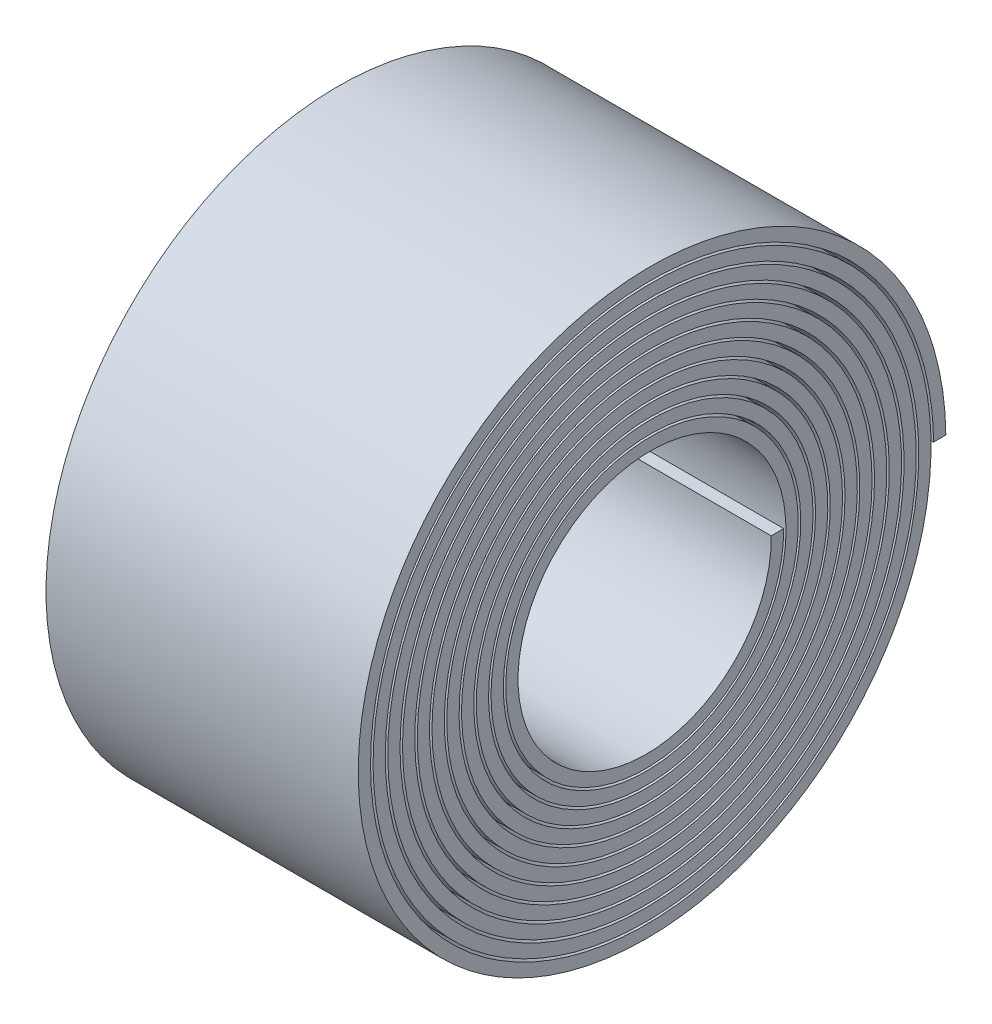
SolidWorks part; units mm, degrees
ref_plane "Front Plane" through (0, 0, 0) normal (0, 0, 1) x (1, 0, 0)
ref_plane "Top Plane" through (0, 0, 0) normal (0, 1, 0) x (1, 0, 0)
ref_plane "Right Plane" through (0, 0, 0) normal (1, 0, 0) x (0, 0, -1)
sketch "Sketch1" plane through (0, 0, 0) normal (1, 0, 0) x (0, 0, -1)
  circle A0 centre (0, 0) radius 2.5
  point P2 (0, 0)
  dimension "D1" = 5
curve "Helix/Spiral1"
sketch "Sketch2" plane through (0, 0, 0) normal (1, 0, 0) x (0, 0, -1)
  line L0 (2.5, 0) -> (2.75, 0.0048)
  line L2 (5.8, 0) -> (6.05, 0.0021)
  spline S0 degree 3 poles (-421.9366, -905.3575) (-57.6424, 57.3436) (7.9155, 8.7178) (1.9401, -1.6929) (1.6038, -2.0262) (0.8018, -2.4743) (0.3373, -2.5884) (-0.5902, -2.5601) (-1.0519, -2.4176) (-1.8406, -1.9113) (-2.1664, -1.5481) (-2.5866, -0.6999) (-2.6802, -0.2161) (-2.6036, 0.7366) (-2.4335, 1.2041) (-1.8725, 1.9894) (-1.4824, 2.3059) (-0.5889, 2.6946) (-0.0868, 2.7661) (0.8885, 2.6388) (1.3604, 2.4401) (2.1387, 1.8236) (2.444, 1.4066) (2.7978, 0.4689) (2.8456, -0.0505) (2.6652, -1.0457) (2.437, -1.5201) (1.7644, -2.2878) (1.3208, -2.58) (0.3402, -2.8954) (-0.1953, -2.9181) (-1.2075, -2.6823) (-1.6827, -2.424) (-2.4362, -1.6949) (-2.7134, -1.2249) (-2.9871, -0.203) (-2.9831, 0.3474) (-2.6898, 1.3734) (-2.4008, 1.8476) (-1.6149, 2.5831) (-1.119, 2.8434) (-0.0577, 3.072) (0.5063, 3.0399) (1.5429, 2.6873) (2.0141, 2.3671) (2.7278, 1.5245) (2.9693, 1.0032) (3.1497, -0.0956) (3.0882, -0.6716) (2.6745, -1.7154) (2.3227, -2.1817) (1.4237, -2.8698) (0.8778, -3.0906) (-0.2563, -3.2195) (-0.8428, -3.1274) (-1.8902, -2.651) (-2.3496, -2.2674) (-3.0082, -1.3126) (-3.2065, -0.7428) (-3.281, 0.4241) (-3.1571, 1.0194) (-2.6168, 2.0667) (-2.2011, 2.5172) (-1.1912, 3.1425) (-0.5985, 3.3164) (0.5985, 3.3336) (1.2009, 3.1767) (2.2444, 2.5714) (2.6838, 2.1236) (3.2719, 1.0598) (3.4197, 0.4451) (3.3768, -0.779) (3.186, -1.3868) (2.5147, -2.4224) (2.035, -2.8487) (0.9184, -3.3959) (0.2831, -3.5158) (-0.9652, -3.4101) (-1.5763, -3.1846) (-2.6001, -2.4467) (-3.0113, -1.9353) (-3.5136, -0.7674) (-3.604, -0.1126) (-3.4331, 1.1565) (-3.172, 1.769) (-2.3671, 2.7768) (-1.8243, 3.1707) (-0.6071, 3.6246) (0.0658, 3.6837) (1.3523, 3.4454) (1.9641, 3.148) (2.9519, 2.276) (3.3264, 1.7023) (3.728, 0.4376) (3.7545, -0.2517) (3.4465, -1.552) (3.1124, -2.1611) (2.1732, -3.1246) (1.5694, -3.4776) (0.2594, -3.8234) (-0.4448, -3.8157) (-1.755, -3.4362) (-2.3591, -3.0649) (-3.2941, -2.0589) (-3.6235, -1.4256) (-3.9101, -0.073) (-3.8667, 0.6444) (-3.414, 1.9607) (-3.0053, 2.5576) (-1.9331, 3.4598) (-1.2712, 3.7636) (0.1214, 3.9875) (0.8501, 3.9072) (2.1683, 3.3799) (2.7558, 2.9334) (3.6209, 1.7959) (3.897, 1.1064) (4.0551, -0.3232) (3.9367, -1.0613) (3.3334, -2.3772) (2.8492, -2.953) (1.6475, -3.7767) (0.9316, -4.0232) (-0.5319, -4.1123) (-1.2774, -3.9547) (-2.5866, -3.2743) (-3.1485, -2.7526) (-3.9265, -1.488) (-4.1414, -0.7469) (-4.1586, 0.7469) (-3.9607, 1.4977) (-3.2027, 2.7959) (-2.6435, 3.3414) (-1.3177, 4.0695) (-0.5529, 4.251) (0.9678, 4.1935) (1.7216, 3.9545) (3.0042, 3.1182) (3.531, 2.522) (4.2051, 1.1369) (4.3513, 0.35) (4.2166, -1.1938) (3.9357, -1.9485) (3.0209, -3.2108) (2.3882, -3.7167) (0.946, -4.3326) (0.1385, -4.4418) (-1.4244, -4.2274) (-2.1776, -3.9039) (-3.415, -2.9106) (-3.8975, -2.2421) (-4.4513, -0.7452) (-4.5218, 0.0811) (-4.2255, 1.6589) (-3.859, 2.4081) (-2.7875, 3.616) (-2.0839, 4.0728) (-0.535, 4.5606) (0.3082, 4.5908) (1.4994, 4.3057) (1.8841, 4.1566) (2.6009, 3.7605) (2.9328, 3.5135) (3.5195, 2.9389) (3.7743, 2.6113) (4.1877, 1.8991) (4.3463, 1.5144) (4.5553, 0.7154) (4.6057, 0.3011) (4.5939, -0.527) (4.5318, -0.9408) (4.299, -1.738) (4.1282, -2.1213) (3.69, -2.8295) (3.4224, -3.1543) (2.8094, -3.7215) (2.464, -3.9638) (1.7198, -4.348) (1.3212, -4.4898) (0.4992, -4.6621) (0.076, -4.6925) (-0.7644, -4.6392) (-1.1815, -4.5554) (-1.9795, -4.279) (-2.3602, -4.0864) (-3.0574, -3.6059) (-3.3738, -3.318) (-3.9191, -2.6671) (-4.1479, -2.3042) (-4.5007, -1.5294) (-4.6248, -1.1175) (-4.7585, -0.2744) (-4.7682, 0.1569) (-4.672, 1.0075) (-4.566, 1.4268) (-4.2455, 2.2231) (-4.0309, 2.5999) (-3.5082, 3.2837) (-3.2001, 3.5905) (-2.5121, 4.1115) (-2.1323, 4.3256) (-1.3281, 4.645) (-0.9038, 4.7503) (-0.0412, 4.8439) (0.397, 4.8322) (1.2556, 4.6919) (1.6759, 4.5634) (2.4681, 4.1982) (2.8398, 3.9616) (3.5077, 3.3969) (3.8037, 3.0688) (4.298, 2.3445) (4.4962, 1.9483) (4.7802, 1.1162) (4.8658, 0.6803) (4.9177, -0.1997) (4.8839, -0.6438) (4.6986, -1.508) (4.5472, -1.9281) (4.137, -2.7137) (3.8783, -3.0791) (3.2719, -3.7285) (2.9242, -4.0124) (2.1646, -4.4778) (1.7527, -4.6591) (0.8942, -4.9056) (0.4477, -4.9707) (-0.4477, -4.9793) (-0.8966, -4.9228) (-1.7641, -4.6916) (-2.1827, -4.517) (-2.9591, -4.0616) (-3.3169, -3.7809) (-3.9454, -3.1333) (-4.216, -2.7664) (-4.6501, -1.9726) (-4.8134, -1.5457) (-5.0206, -0.6626) (-5.0643, -0.2064) (-5.0282, 0.7022) (-4.9485, 1.1547) (-4.6707, 2.0231) (-4.4726, 2.4389) (-3.972, 3.2036) (-3.6694, 3.5525) (-2.9812, 4.1575) (-2.5956, 4.4136) (-1.7688, 4.8141) (-1.3277, 4.9585) (-0.4218, 5.1244) (0.043, 5.146) (0.9626, 5.064) (1.4175, 4.9605) (2.2841, 4.6354) (2.6959, 4.4138) (3.4463, 3.868) (3.7849, 3.5438) (4.364, 2.8157) (4.6044, 2.4119) (4.9693, 1.5536) (5.0936, 1.0992) (5.2166, 0.1724) (5.2152, -0.2999) (5.0862, -1.2282) (4.9585, -1.6841) (4.5857, -2.5465) (4.3404, -2.9529) (3.7496, -3.6864) (3.404, -4.0135) (2.637, -4.5641) (2.2157, -4.7877) (1.3274, -5.1147) (0.8606, -5.218) (-0.085, -5.2964) (-0.5637, -5.2714) (-1.4982, -5.0943) (-1.954, -4.9421) (-2.8095, -4.5211) (-3.2091, -4.2523) (-3.9231, -3.6168) (-4.2373, -3.2502) (-4.7571, -2.4454) (-4.9627, -2.0072) (-5.2497, -1.0907) (-5.3311, -0.6124) (-5.3633, 0.3498) (-5.3141, 0.8337) (-5.088, 1.7719) (-4.911, 2.2262) (-4.4417, 3.0721) (-4.1493, 3.4637) (-3.4697, 4.1554) (-3.0826, 4.4555) (-2.2411, 4.9421) (-1.7868, 5.1285) (-0.8438, 5.3736) (-0.3551, 5.4322) (0.6214, 5.4168) (1.1092, 5.3428) (2.0485, 5.0669) (2.5, 4.865) (3.3336, 4.3472) (3.7157, 4.0315) (4.3826, 3.3085) (4.6674, 2.9012) (5.1183, 2.0245) (5.2845, 1.555) (5.4857, 0.5874) (5.5208, 0.0894) (5.4565, -0.8991) (5.3571, -1.3896) (5.0307, -2.3273) (4.8037, -2.7745) (4.2377, -3.5931) (3.8987, -3.9644) (3.1331, -4.6039) (2.7064, -4.872) (1.7959, -5.285) (1.312, -5.4299) (0.322, -5.5855) (-0.1842, -5.5961) (-1.1821, -5.4817) (-1.6739, -5.3566) (-2.6074, -4.9793) (-3.049, -4.727) (-3.8498, -4.1129) (-4.2089, -3.7512) (-4.8184, -2.9439) (-5.0686, -2.4985) (-5.4414, -1.5557) (-5.5641, -1.0585) (-5.6722, -0.0482) (-5.6577, 0.4649) (-5.4921, 1.4698) (-5.3409, 1.9615) (-4.9123, 2.8879) (-4.6348, 3.3225) (-3.9731, 4.1028) (-3.5889, 4.4484) (-2.7411, 5.0252) (-2.2776, 5.2563) (-1.3045, 5.5868) (-0.795, 5.6862) (0.2334, 5.7453) (0.7521, 5.7051) (1.7612, 5.4873) (2.2515, 5.3097) (3.1681, 4.8296) (3.5942, 4.527) (4.3511, 3.8182) (4.6819, 3.412) (5.2235, 2.525) (5.4344, 2.0443) (11.0299, -17.545) (-82.1193, -65.6208) (-440.9328, 894.6492) knots -0.190622 -0.190622 -0.190622 -0.190622 0.007812 0.007812 0.015625 0.015625 0.023438 0.023438 0.03125 0.03125 0.039063 0.039063 0.046875 0.046875 0.054687 0.054687 0.0625 0.0625 0.070312 0.070312 0.078125 0.078125 0.085937 0.085937 0.09375 0.09375 0.101562 0.101562 0.109375 0.109375 0.117187 0.117187 0.125 0.125 0.132812 0.132812 0.140625 0.140625 0.148437 0.148437 0.15625 0.15625 0.164062 0.164062 0.171875 0.171875 0.179687 0.179687 0.1875 0.1875 0.195312 0.195312 0.203125 0.203125 0.210937 0.210937 0.21875 0.21875 0.226562 0.226562 0.234375 0.234375 0.242187 0.242187 0.25 0.25 0.257812 0.257812 0.265625 0.265625 0.273438 0.273438 0.28125 0.28125 0.289062 0.289062 0.296875 0.296875 0.304688 0.304688 0.3125 0.3125 0.320312 0.320312 0.328125 0.328125 0.335938 0.335938 0.34375 0.34375 0.351562 0.351562 0.359375 0.359375 0.367188 0.367188 0.375 0.375 0.382812 0.382812 0.390625 0.390625 0.398438 0.398438 0.40625 0.40625 0.414062 0.414062 0.421875 0.421875 0.429688 0.429688 0.4375 0.4375 0.445312 0.445312 0.453125 0.453125 0.460938 0.460938 0.46875 0.46875 0.476562 0.476562 0.484375 0.484375 0.492188 0.492188 0.5 0.5 0.507812 0.507812 0.515625 0.515625 0.523438 0.523438 0.53125 0.53125 0.539062 0.539062 0.546875 0.546875 0.554688 0.554688 0.5625 0.5625 0.570312 0.570312 0.578125 0.578125 0.585938 0.585938 0.59375 0.59375 0.601562 0.601562 0.609375 0.609375 0.617188 0.617188 0.621094 0.621094 0.625 0.625 0.628906 0.628906 0.632812 0.632812 0.636719 0.636719 0.640625 0.640625 0.644531 0.644531 0.648438 0.648438 0.652344 0.652344 0.65625 0.65625 0.660156 0.660156 0.664062 0.664062 0.667969 0.667969 0.671875 0.671875 0.675781 0.675781 0.679688 0.679688 0.683594 0.683594 0.6875 0.6875 0.691406 0.691406 0.695312 0.695312 0.699219 0.699219 0.703125 0.703125 0.707031 0.707031 0.710938 0.710938 0.714844 0.714844 0.71875 0.71875 0.722656 0.722656 0.726562 0.726562 0.730469 0.730469 0.734375 0.734375 0.738281 0.738281 0.742188 0.742188 0.746094 0.746094 0.75 0.75 0.753906 0.753906 0.757812 0.757812 0.761719 0.761719 0.765625 0.765625 0.769531 0.769531 0.773438 0.773438 0.777344 0.777344 0.78125 0.78125 0.785156 0.785156 0.789062 0.789062 0.792969 0.792969 0.796875 0.796875 0.800781 0.800781 0.804688 0.804688 0.808594 0.808594 0.8125 0.8125 0.816406 0.816406 0.820312 0.820312 0.824219 0.824219 0.828125 0.828125 0.832031 0.832031 0.835938 0.835938 0.839844 0.839844 0.84375 0.84375 0.847656 0.847656 0.851562 0.851562 0.855469 0.855469 0.859375 0.859375 0.863281 0.863281 0.867188 0.867188 0.871094 0.871094 0.875 0.875 0.878906 0.878906 0.882812 0.882812 0.886719 0.886719 0.890625 0.890625 0.894531 0.894531 0.898438 0.898438 0.902344 0.902344 0.90625 0.90625 0.910156 0.910156 0.914062 0.914062 0.917969 0.917969 0.921875 0.921875 0.925781 0.925781 0.929688 0.929688 0.933594 0.933594 0.9375 0.9375 0.941406 0.941406 0.945312 0.945312 0.949219 0.949219 0.953125 0.953125 0.957031 0.957031 0.960938 0.960938 0.964844 0.964844 0.96875 0.96875 0.972656 0.972656 0.976562 0.976562 0.980469 0.980469 0.984375 0.984375 0.988281 0.988281 0.992188 0.992188 0.996094 0.996094 1.144987 1.144987 1.144987 1.144987 only from (2.5, 0) to (5.8, 0) construction
  spline S1 degree 3 poles (2.5, 0) (2.5086, -0.45) (2.3928, -0.9042) (1.9401, -1.6929) (1.6038, -2.0262) (0.8018, -2.4743) (0.3373, -2.5884) (-0.5902, -2.5601) (-1.0519, -2.4176) (-1.8406, -1.9113) (-2.1664, -1.5481) (-2.5866, -0.6999) (-2.6802, -0.2161) (-2.6036, 0.7366) (-2.4335, 1.2041) (-1.8725, 1.9894) (-1.4824, 2.3059) (-0.5889, 2.6946) (-0.0868, 2.7661) (0.8885, 2.6388) (1.3604, 2.4401) (2.1387, 1.8236) (2.444, 1.4066) (2.7978, 0.4689) (2.8456, -0.0505) (2.6652, -1.0457) (2.437, -1.5201) (1.7644, -2.2878) (1.3208, -2.58) (0.3402, -2.8954) (-0.1953, -2.9181) (-1.2075, -2.6823) (-1.6827, -2.424) (-2.4362, -1.6949) (-2.7134, -1.2249) (-2.9871, -0.203) (-2.9831, 0.3474) (-2.6898, 1.3734) (-2.4008, 1.8476) (-1.6149, 2.5831) (-1.119, 2.8434) (-0.0577, 3.072) (0.5063, 3.0399) (1.5429, 2.6873) (2.0141, 2.3671) (2.7278, 1.5245) (2.9693, 1.0032) (3.1497, -0.0956) (3.0882, -0.6716) (2.6745, -1.7154) (2.3227, -2.1817) (1.4237, -2.8698) (0.8778, -3.0906) (-0.2563, -3.2195) (-0.8428, -3.1274) (-1.8902, -2.651) (-2.3496, -2.2674) (-3.0082, -1.3126) (-3.2065, -0.7428) (-3.281, 0.4241) (-3.1571, 1.0194) (-2.6168, 2.0667) (-2.2011, 2.5172) (-1.1912, 3.1425) (-0.5985, 3.3164) (0.5985, 3.3336) (1.2009, 3.1767) (2.2444, 2.5714) (2.6838, 2.1236) (3.2719, 1.0598) (3.4197, 0.4451) (3.3768, -0.779) (3.186, -1.3868) (2.5147, -2.4224) (2.035, -2.8487) (0.9184, -3.3959) (0.2831, -3.5158) (-0.9652, -3.4101) (-1.5763, -3.1846) (-2.6001, -2.4467) (-3.0113, -1.9353) (-3.5136, -0.7674) (-3.604, -0.1126) (-3.4331, 1.1565) (-3.172, 1.769) (-2.3671, 2.7768) (-1.8243, 3.1707) (-0.6071, 3.6246) (0.0658, 3.6837) (1.3523, 3.4454) (1.9641, 3.148) (2.9519, 2.276) (3.3264, 1.7023) (3.728, 0.4376) (3.7545, -0.2517) (3.4465, -1.552) (3.1124, -2.1611) (2.1732, -3.1246) (1.5694, -3.4776) (0.2594, -3.8234) (-0.4448, -3.8157) (-1.755, -3.4362) (-2.3591, -3.0649) (-3.2941, -2.0589) (-3.6235, -1.4256) (-3.9101, -0.073) (-3.8667, 0.6444) (-3.414, 1.9607) (-3.0053, 2.5576) (-1.9331, 3.4598) (-1.2712, 3.7636) (0.1214, 3.9875) (0.8501, 3.9072) (2.1683, 3.3799) (2.7558, 2.9334) (3.6209, 1.7959) (3.897, 1.1064) (4.0551, -0.3232) (3.9367, -1.0613) (3.3334, -2.3772) (2.8492, -2.953) (1.6475, -3.7767) (0.9316, -4.0232) (-0.5319, -4.1123) (-1.2774, -3.9547) (-2.5866, -3.2743) (-3.1485, -2.7526) (-3.9265, -1.488) (-4.1414, -0.7469) (-4.1586, 0.7469) (-3.9607, 1.4977) (-3.2027, 2.7959) (-2.6435, 3.3414) (-1.3177, 4.0695) (-0.5529, 4.251) (0.9678, 4.1935) (1.7216, 3.9545) (3.0042, 3.1182) (3.531, 2.522) (4.2051, 1.1369) (4.3513, 0.35) (4.2166, -1.1938) (3.9357, -1.9485) (3.0209, -3.2108) (2.3882, -3.7167) (0.946, -4.3326) (0.1385, -4.4418) (-1.4244, -4.2274) (-2.1776, -3.9039) (-3.415, -2.9106) (-3.8975, -2.2421) (-4.4513, -0.7452) (-4.5218, 0.0811) (-4.2255, 1.6589) (-3.859, 2.4081) (-2.7875, 3.616) (-2.0839, 4.0728) (-0.535, 4.5606) (0.3082, 4.5908) (1.4994, 4.3057) (1.8841, 4.1566) (2.6009, 3.7605) (2.9328, 3.5135) (3.5195, 2.9389) (3.7743, 2.6113) (4.1877, 1.8991) (4.3463, 1.5144) (4.5553, 0.7154) (4.6057, 0.3011) (4.5939, -0.527) (4.5318, -0.9408) (4.299, -1.738) (4.1282, -2.1213) (3.69, -2.8295) (3.4224, -3.1543) (2.8094, -3.7215) (2.464, -3.9638) (1.7198, -4.348) (1.3212, -4.4898) (0.4992, -4.6621) (0.076, -4.6925) (-0.7644, -4.6392) (-1.1815, -4.5554) (-1.9795, -4.279) (-2.3602, -4.0864) (-3.0574, -3.6059) (-3.3738, -3.318) (-3.9191, -2.6671) (-4.1479, -2.3042) (-4.5007, -1.5294) (-4.6248, -1.1175) (-4.7585, -0.2744) (-4.7682, 0.1569) (-4.672, 1.0075) (-4.566, 1.4268) (-4.2455, 2.2231) (-4.0309, 2.5999) (-3.5082, 3.2837) (-3.2001, 3.5905) (-2.5121, 4.1115) (-2.1323, 4.3256) (-1.3281, 4.645) (-0.9038, 4.7503) (-0.0412, 4.8439) (0.397, 4.8322) (1.2556, 4.6919) (1.6759, 4.5634) (2.4681, 4.1982) (2.8398, 3.9616) (3.5077, 3.3969) (3.8037, 3.0688) (4.298, 2.3445) (4.4962, 1.9483) (4.7802, 1.1162) (4.8658, 0.6803) (4.9177, -0.1997) (4.8839, -0.6438) (4.6986, -1.508) (4.5472, -1.9281) (4.137, -2.7137) (3.8783, -3.0791) (3.2719, -3.7285) (2.9242, -4.0124) (2.1646, -4.4778) (1.7527, -4.6591) (0.8942, -4.9056) (0.4477, -4.9707) (-0.4477, -4.9793) (-0.8966, -4.9228) (-1.7641, -4.6916) (-2.1827, -4.517) (-2.9591, -4.0616) (-3.3169, -3.7809) (-3.9454, -3.1333) (-4.216, -2.7664) (-4.6501, -1.9726) (-4.8134, -1.5457) (-5.0206, -0.6626) (-5.0643, -0.2064) (-5.0282, 0.7022) (-4.9485, 1.1547) (-4.6707, 2.0231) (-4.4726, 2.4389) (-3.972, 3.2036) (-3.6694, 3.5525) (-2.9812, 4.1575) (-2.5956, 4.4136) (-1.7688, 4.8141) (-1.3277, 4.9585) (-0.4218, 5.1244) (0.043, 5.146) (0.9626, 5.064) (1.4175, 4.9605) (2.2841, 4.6354) (2.6959, 4.4138) (3.4463, 3.868) (3.7849, 3.5438) (4.364, 2.8157) (4.6044, 2.4119) (4.9693, 1.5536) (5.0936, 1.0992) (5.2166, 0.1724) (5.2152, -0.2999) (5.0862, -1.2282) (4.9585, -1.6841) (4.5857, -2.5465) (4.3404, -2.9529) (3.7496, -3.6864) (3.404, -4.0135) (2.637, -4.5641) (2.2157, -4.7877) (1.3274, -5.1147) (0.8606, -5.218) (-0.085, -5.2964) (-0.5637, -5.2714) (-1.4982, -5.0943) (-1.954, -4.9421) (-2.8095, -4.5211) (-3.2091, -4.2523) (-3.9231, -3.6168) (-4.2373, -3.2502) (-4.7571, -2.4454) (-4.9627, -2.0072) (-5.2497, -1.0907) (-5.3311, -0.6124) (-5.3633, 0.3498) (-5.3141, 0.8337) (-5.088, 1.7719) (-4.911, 2.2262) (-4.4417, 3.0721) (-4.1493, 3.4637) (-3.4697, 4.1554) (-3.0826, 4.4555) (-2.2411, 4.9421) (-1.7868, 5.1285) (-0.8438, 5.3736) (-0.3551, 5.4322) (0.6214, 5.4168) (1.1092, 5.3428) (2.0485, 5.0669) (2.5, 4.865) (3.3336, 4.3472) (3.7157, 4.0315) (4.3826, 3.3085) (4.6674, 2.9012) (5.1183, 2.0245) (5.2845, 1.555) (5.4857, 0.5874) (5.5208, 0.0894) (5.4565, -0.8991) (5.3571, -1.3896) (5.0307, -2.3273) (4.8037, -2.7745) (4.2377, -3.5931) (3.8987, -3.9644) (3.1331, -4.6039) (2.7064, -4.872) (1.7959, -5.285) (1.312, -5.4299) (0.322, -5.5855) (-0.1842, -5.5961) (-1.1821, -5.4817) (-1.6739, -5.3566) (-2.6074, -4.9793) (-3.049, -4.727) (-3.8498, -4.1129) (-4.2089, -3.7512) (-4.8184, -2.9439) (-5.0686, -2.4985) (-5.4414, -1.5557) (-5.5641, -1.0585) (-5.6722, -0.0482) (-5.6577, 0.4649) (-5.4921, 1.4698) (-5.3409, 1.9615) (-4.9123, 2.8879) (-4.6348, 3.3225) (-3.9731, 4.1028) (-3.5889, 4.4484) (-2.7411, 5.0252) (-2.2776, 5.2563) (-1.3045, 5.5868) (-0.795, 5.6862) (0.2334, 5.7453) (0.7521, 5.7051) (1.7612, 5.4873) (2.2515, 5.3097) (3.1681, 4.8296) (3.5942, 4.527) (4.3511, 3.8182) (4.6819, 3.412) (5.2235, 2.525) (5.4344, 2.0443) (5.7205, 1.0427) (5.7957, 0.522) (5.8, 0) knots 0 0 0 0 0.007812 0.007812 0.015625 0.015625 0.023438 0.023438 0.03125 0.03125 0.039063 0.039063 0.046875 0.046875 0.054687 0.054687 0.0625 0.0625 0.070312 0.070312 0.078125 0.078125 0.085937 0.085937 0.09375 0.09375 0.101562 0.101562 0.109375 0.109375 0.117187 0.117187 0.125 0.125 0.132812 0.132812 0.140625 0.140625 0.148437 0.148437 0.15625 0.15625 0.164062 0.164062 0.171875 0.171875 0.179687 0.179687 0.1875 0.1875 0.195312 0.195312 0.203125 0.203125 0.210937 0.210937 0.21875 0.21875 0.226562 0.226562 0.234375 0.234375 0.242187 0.242187 0.25 0.25 0.257812 0.257812 0.265625 0.265625 0.273438 0.273438 0.28125 0.28125 0.289062 0.289062 0.296875 0.296875 0.304688 0.304688 0.3125 0.3125 0.320312 0.320312 0.328125 0.328125 0.335938 0.335938 0.34375 0.34375 0.351562 0.351562 0.359375 0.359375 0.367188 0.367188 0.375 0.375 0.382812 0.382812 0.390625 0.390625 0.398438 0.398438 0.40625 0.40625 0.414062 0.414062 0.421875 0.421875 0.429688 0.429688 0.4375 0.4375 0.445312 0.445312 0.453125 0.453125 0.460938 0.460938 0.46875 0.46875 0.476562 0.476562 0.484375 0.484375 0.492188 0.492188 0.5 0.5 0.507812 0.507812 0.515625 0.515625 0.523438 0.523438 0.53125 0.53125 0.539062 0.539062 0.546875 0.546875 0.554688 0.554688 0.5625 0.5625 0.570312 0.570312 0.578125 0.578125 0.585938 0.585938 0.59375 0.59375 0.601562 0.601562 0.609375 0.609375 0.617188 0.617188 0.621094 0.621094 0.625 0.625 0.628906 0.628906 0.632812 0.632812 0.636719 0.636719 0.640625 0.640625 0.644531 0.644531 0.648438 0.648438 0.652344 0.652344 0.65625 0.65625 0.660156 0.660156 0.664062 0.664062 0.667969 0.667969 0.671875 0.671875 0.675781 0.675781 0.679688 0.679688 0.683594 0.683594 0.6875 0.6875 0.691406 0.691406 0.695312 0.695312 0.699219 0.699219 0.703125 0.703125 0.707031 0.707031 0.710938 0.710938 0.714844 0.714844 0.71875 0.71875 0.722656 0.722656 0.726562 0.726562 0.730469 0.730469 0.734375 0.734375 0.738281 0.738281 0.742188 0.742188 0.746094 0.746094 0.75 0.75 0.753906 0.753906 0.757812 0.757812 0.761719 0.761719 0.765625 0.765625 0.769531 0.769531 0.773438 0.773438 0.777344 0.777344 0.78125 0.78125 0.785156 0.785156 0.789062 0.789062 0.792969 0.792969 0.796875 0.796875 0.800781 0.800781 0.804688 0.804688 0.808594 0.808594 0.8125 0.8125 0.816406 0.816406 0.820312 0.820312 0.824219 0.824219 0.828125 0.828125 0.832031 0.832031 0.835938 0.835938 0.839844 0.839844 0.84375 0.84375 0.847656 0.847656 0.851562 0.851562 0.855469 0.855469 0.859375 0.859375 0.863281 0.863281 0.867188 0.867188 0.871094 0.871094 0.875 0.875 0.878906 0.878906 0.882812 0.882812 0.886719 0.886719 0.890625 0.890625 0.894531 0.894531 0.898438 0.898438 0.902344 0.902344 0.90625 0.90625 0.910156 0.910156 0.914062 0.914062 0.917969 0.917969 0.921875 0.921875 0.925781 0.925781 0.929688 0.929688 0.933594 0.933594 0.9375 0.9375 0.941406 0.941406 0.945312 0.945312 0.949219 0.949219 0.953125 0.953125 0.957031 0.957031 0.960938 0.960938 0.964844 0.964844 0.96875 0.96875 0.972656 0.972656 0.976562 0.976562 0.980469 0.980469 0.984375 0.984375 0.988281 0.988281 0.992188 0.992188 0.996094 0.996094 1 1 1 1
  spline S2 degree 1 poles (2.75, 0.0048) (6.05, 0.0021) knots 0 0 1 1 construction
  spline S3 degree 3 poles (2.75, 0.0048) (2.7593, -0.4865) (2.5044, -1.4912) (1.395, -2.5887) (-0.1359, -2.9651) (-1.656, -2.4957) (-2.7279, -1.3009) (-3.0355, 0.2893) (-2.4766, 1.8249) (-1.1964, 2.8635) (0.45, 3.098) (1.9958, 2.4468) (2.9953, 1.0817) (3.1518, -0.6174) (2.406, -2.1681) (0.9569, -3.1225) (-0.7912, -3.1964) (-2.3411, -2.354) (-3.2445, -0.8221) (-3.2314, 0.9707) (-2.2908, 2.514) (-0.6777, 3.3605) (1.1556, 3.2563) (2.6862, 2.2161) (3.4701, 0.5238) (3.2706, -1.3451) (2.1299, -2.857) (0.3607, -3.5724) (-1.5388, -3.2741) (-3.0256, -2.0322) (-3.6669, -0.1889) (-3.2662, 1.7359) (-1.9229, 3.1914) (-0.0086, 3.753) (1.9359, 3.2467) (3.3535, 1.8022) (3.83, -0.1796) (3.2152, -2.1381) (1.6701, -3.5113) (-0.3753, -3.8973) (-2.3417, -3.1716) (-3.6641, -1.5268) (-3.9545, 0.5781) (-3.1156, 2.5461) (-1.3725, 3.8111) (0.7874, 4.001) (2.7505, 3.047) (3.9516, 1.2073) (4.0363, -1.0025) (2.9658, -2.9541) (1.0316, -4.0848) (-1.223, -4.0599) (-3.1563, -2.8717) (-4.2102, -0.8457) (-4.0714, 1.4482) (-2.7648, 3.3562) (-0.65, 4.3269) (1.6773, 4.0705) (3.5531, 2.6451) (4.4344, 0.4448) (4.0566, -1.9098) (2.5127, -3.7462) (0.2306, -4.532) (-2.1449, -4.0296) (-3.9346, -2.3675) (-4.619, -0.0079) (-3.9891, 2.3818) (-2.2098, 4.1177) (0.2228, 4.695) (2.6198, 3.9349) (4.2946, 2.0398) (4.7592, -0.4609) (3.8668, -2.8582) (1.8576, -4.4645) (-0.7059, -4.8111) (-3.096, -3.7847) (-4.6267, -1.6636) (-4.8503, 0.957) (-3.6883, 3.3326) (-1.4581, 4.7805) (1.2136, 4.8763) (3.567, 3.5777) (4.9251, 1.2415) (4.8885, -1.475) (3.4529, -3.7984) (1.0141, -5.0597) (-1.7405, -4.8867) (-4.0261, -3.3138) (-5.1837, -0.7765) (-4.8704, 2.0093) (-3.1606, 4.2491) (-0.5292, 5.2964) (2.2806, 4.8393) (4.4666, 2.9934) (5.397, 0.2726) (4.7932, -2.5536) (2.8123, -4.6777) (0.0074, -5.4851) (-2.8275, -4.7317) (-4.8817, -2.6177) (-5.56, 0.2658) (-4.6548, 3.1014) (-2.4097, 5.0777) (0.5463, 5.621) (3.3745, 4.5622) (5.2648, 2.1887) (5.6678, -0.8334) (4.4539, -3.6458) (1.955, -5.4423) (-1.1264, -5.6997) (-3.9145, -4.3298) (-5.6094, -1.7091) (-5.7163, 1.4244) (-4.1899, 4.1797) (-1.4515, 5.7653) (1.7268, 5.7172) (4.4404, 4.0342) (5.9092, 1.1827) (5.702, -2.0326) (3.863, -4.6958) (0.9032, -6.0405) (-2.3411, -5.6704) (-4.9449, -3.6762) (-6.1583, -0.6137) (-5.6221, 2.6513) (-3.4743, 5.1867) (-0.3147, 6.2626) (2.9622, 5.555) (5.4207, 3.2642) (6.0412, 1.0755) (6.05, 0.0021) knots 0 0 0 0 0.007812 0.015625 0.023438 0.03125 0.039062 0.046875 0.054688 0.0625 0.070312 0.078125 0.085938 0.09375 0.101562 0.109375 0.117188 0.125 0.132812 0.140625 0.148438 0.15625 0.164062 0.171875 0.179688 0.1875 0.195312 0.203125 0.210938 0.21875 0.226562 0.234375 0.242188 0.25 0.257812 0.265625 0.273438 0.28125 0.289062 0.296875 0.304688 0.3125 0.320312 0.328125 0.335938 0.34375 0.351562 0.359375 0.367188 0.375 0.382812 0.390625 0.398438 0.40625 0.414062 0.421875 0.429688 0.4375 0.445312 0.453125 0.460938 0.46875 0.476562 0.484375 0.492188 0.5 0.507812 0.515625 0.523438 0.53125 0.539062 0.546875 0.554688 0.5625 0.570312 0.578125 0.585938 0.59375 0.601562 0.609375 0.617188 0.625 0.632812 0.640625 0.648438 0.65625 0.664062 0.671875 0.679688 0.6875 0.695312 0.703125 0.710938 0.71875 0.726562 0.734375 0.742188 0.75 0.757812 0.765625 0.773438 0.78125 0.789062 0.796875 0.804688 0.8125 0.820312 0.828125 0.835938 0.84375 0.851562 0.859375 0.867188 0.875 0.882812 0.890625 0.898438 0.90625 0.914062 0.921875 0.929688 0.9375 0.945312 0.953125 0.960938 0.96875 0.976562 0.984375 0.992188 1 1 1 1
  point P1 (0, 0)
  point P5 (0, 0)
  point P7 (0, 0)
  point P8 (0, 0)
  dimension "D1" = 0.25
extrude "Boss-Extrude1" add sketch "Sketch2" along normal mid plane 6.35
